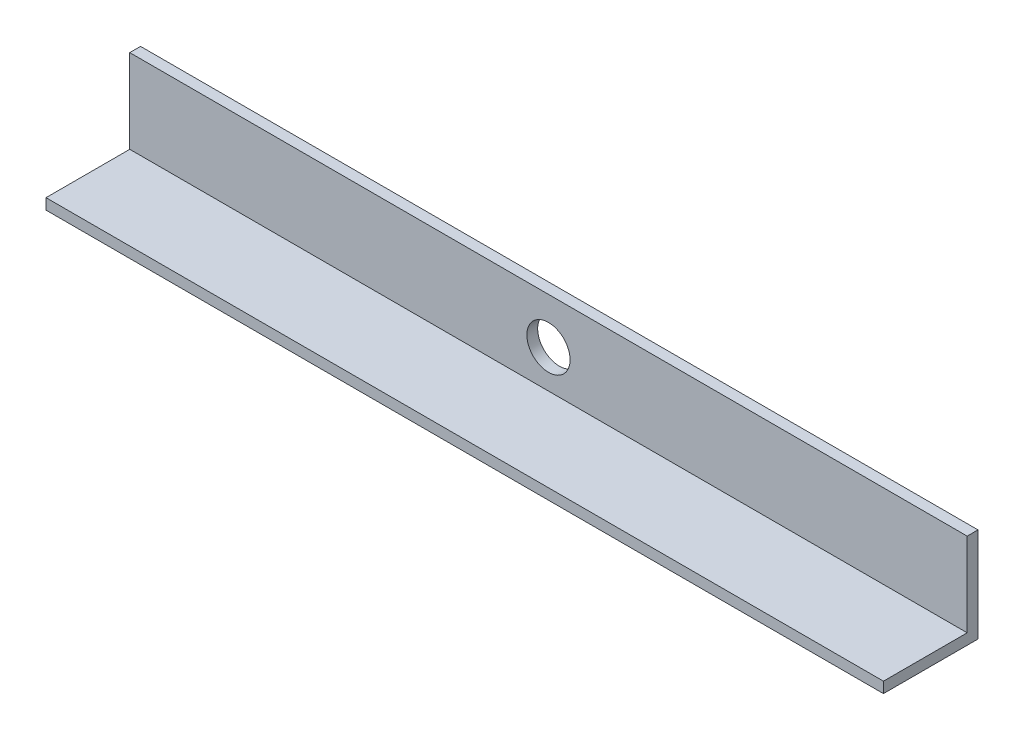
SolidWorks part; units mm, degrees
ref_plane "Спереди" through (0, 0, 0) normal (0, 0, 1) x (1, 0, 0)
ref_plane "Сверху" through (0, 0, 0) normal (0, 1, 0) x (1, 0, 0)
ref_plane "Справа" through (0, 0, 0) normal (1, 0, 0) x (0, 0, -1)
sketch "Эскиз1" plane through (0, 0, 0) normal (1, 0, 0) x (0, 0, -1)
  line L0 (0, 35) -> (0, 0)
  line L1 (0, 0) -> (-35, 0)
extrude "Вытянуть-Тонкостенный1" add sketch "Эскиз1" along normal blind 310 thin thin type one direction wall 4
sketch "Эскиз2" plane through (0, 0, 0) normal (0, 0, -1) x (-1, 0, 0)
  circle A0 centre (-155, 18) radius 8
extrude "Вырез-Вытянуть1" cut sketch "Эскиз2" against normal blind 10
